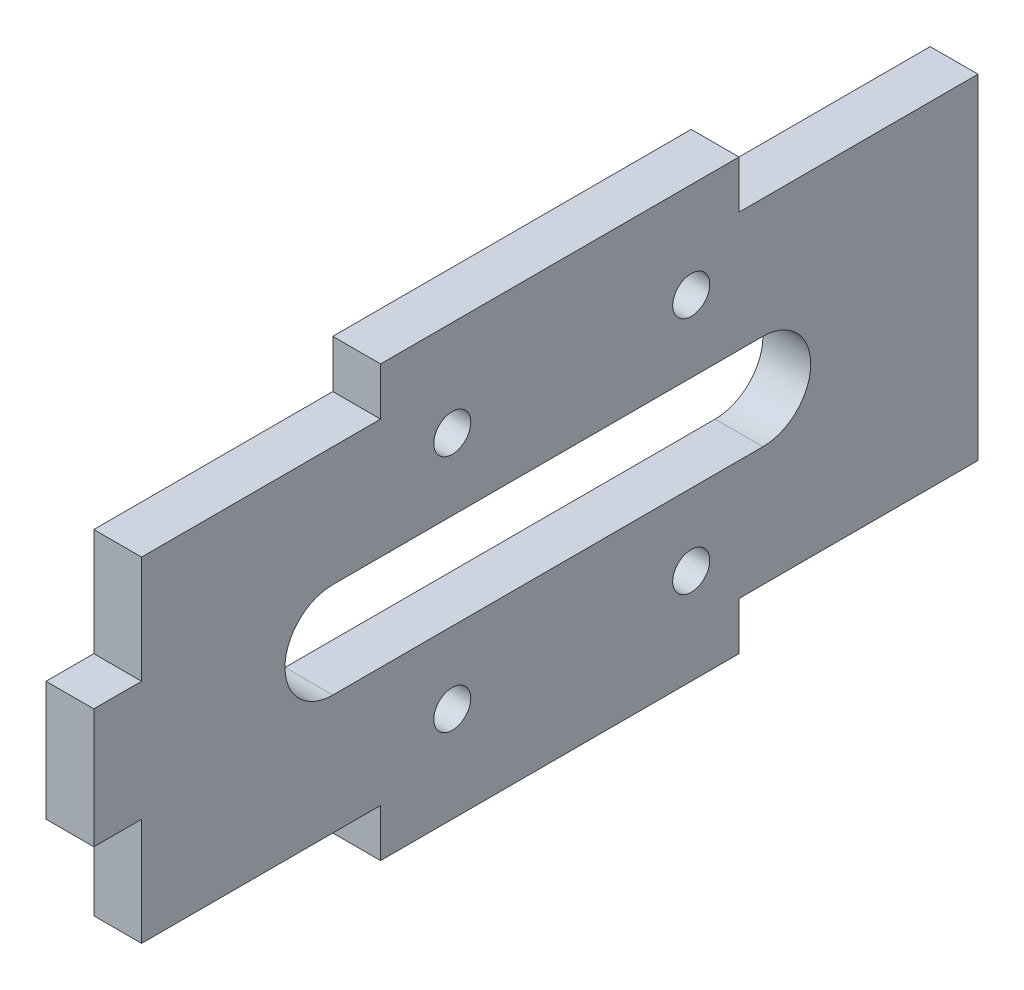
SolidWorks part; units mm, degrees
ref_plane "Front" through (0, 0, 0) normal (0, 0, 1) x (1, 0, 0)
ref_plane "Top" through (0, 0, 0) normal (0, 1, 0) x (1, 0, 0)
ref_plane "Right" through (0, 0, 0) normal (1, 0, 0) x (0, 0, -1)
sketch "Skizze1" plane through (0, 0, 0) normal (1, 0, 0) x (0, 0, -1)
  line L0 (0, 0) -> (74, 0) construction
  line L1 (0, -5) -> (0, 5)
  line L2 (0, 5) -> (4, 5)
  line L3 (4, 5) -> (4, 18)
  line L4 (4, 18) -> (74, 18)
  line L5 (74, 18) -> (74, -18)
  line L6 (4, -18) -> (74, -18)
  line L7 (4, -5) -> (4, -18)
  line L8 (0, -5) -> (4, -5)
  dimension "D1" = 4
  dimension "D2" = 10
  dimension "D3" = 36
  dimension "D4" = 70
extrude "Grundplatte" add sketch "Skizze1" along normal blind 4
sketch "Skizze2" plane through (4, 0, 0) normal (1, 0, 0) x (0, 0, -1)
  line L0 (39, 18) -> (39, 0) construction
  line L1 (4, 18) -> (24, 18)
  line L2 (4, 18) -> (4, 14)
  line L3 (4, 14) -> (24, 14)
  line L4 (24, 18) -> (24, 14)
  line L5 (74, 18) -> (54, 18)
  line L6 (74, 18) -> (74, 14)
  line L7 (74, 14) -> (54, 14)
  line L8 (54, 18) -> (54, 14)
  line L9 (74, 18) -> (4, 18) construction
  line L10 (39, 0) -> (0, 0) construction
  line L11 (54, -18) -> (54, -14)
  line L12 (74, -14) -> (54, -14)
  line L13 (74, -18) -> (74, -14)
  line L14 (74, -18) -> (54, -18)
  line L15 (24, -18) -> (24, -14)
  line L16 (4, -14) -> (24, -14)
  line L17 (4, -18) -> (4, -14)
  line L18 (4, -18) -> (24, -18)
  dimension "D1" = 4
  dimension "D2" = 30
extrude "Schnitt-Linear austragen1" cut sketch "Skizze2" against normal through all
sketch "Skizze3" [suppressed] plane through (4, 0, 0) normal (1, 0, 0) x (0, 0, -1)
  line L0 (74, 15) -> (4, 15) construction
  line L1 (24, 15) -> (54, 15)
  line L2 (24, 15) -> (24, 11)
  line L3 (24, 11) -> (54, 11)
  line L4 (54, 15) -> (54, 11)
  line L5 (39, -15) -> (39, 11) construction
  line L6 (4, -15) -> (74, -15) construction
  dimension "D1" = 4
  dimension "D2" = 30
extrude "Schnitt-Linear austragen2" [suppressed] cut sketch "Skizze3" against normal through all
sketch "Skizze4" plane through (4, 0, 0) normal (1, 0, 0) x (0, 0, -1)
  line L0 (0, 0) -> (40, 0) construction
  line L1 (50, 10) -> (30, 10) construction
  line L2 (50, 10) -> (50, -10) construction
  line L3 (50, -10) -> (30, -10) construction
  line L4 (30, 10) -> (30, -10) construction
  line L5 (50, 10) -> (30, -10) construction
  line L6 (50, -10) -> (30, 10) construction
  line L7 (0, 5) -> (0, -5) construction
  circle A0 centre (50, 10) radius 1.55
  circle A1 centre (30, 10) radius 1.55
  circle A2 centre (30, -10) radius 1.55
  circle A3 centre (50, -10) radius 1.55
  point P0 (40, 0)
  dimension "D3" = 3.1
  dimension "D1" = 20
  dimension "D2" = 20
  dimension "D4" = 40
extrude "Schnitt-Linear austragen3" cut sketch "Skizze4" against normal blind 10
fillet "Verrundung1" [suppressed] radius 20
sketch "Skizze5" [suppressed] plane through (4, 0, 0) normal (1, 0, 0) x (0, 0, -1)
  line L0 (20, 0) -> (38, 0) construction
  line L1 (38, 0) -> (56, 0) construction
  line L2 (0, 5) -> (0, -5) construction
  line L3 (0, 0) -> (20, 0) construction
  circle A0 centre (20, 0) radius 7.5
  circle A1 centre (56, 0) radius 7.5
  circle A2 centre (38, 0) radius 5
  dimension "D1" = 15
  dimension "D2" = 10
  dimension "D3" = 18
  dimension "D4" = 20
extrude "Löcher" [suppressed] cut sketch "Skizze5" against normal through all
sketch "Skizze6" plane through (4, 0, 0) normal (1, 0, 0) x (0, 0, -1)
  line L0 (20, 0) -> (56, 0) construction
  line L1 (20, 4) -> (56, 4)
  line L2 (20, -4) -> (56, -4)
  line L3 (4, 14) -> (4, 5) construction
  arc A0 (20, 4) -> (20, -4) centre (20, 0) ccw
  arc A1 (56, -4) -> (56, 4) centre (56, 0) ccw
  point P3 (38, 0)
  dimension "D1" = 4
  dimension "D2" = 36
  dimension "D3" = 16
extrude "Schnitt-Linear austragen5" cut sketch "Skizze6" against normal blind 10
